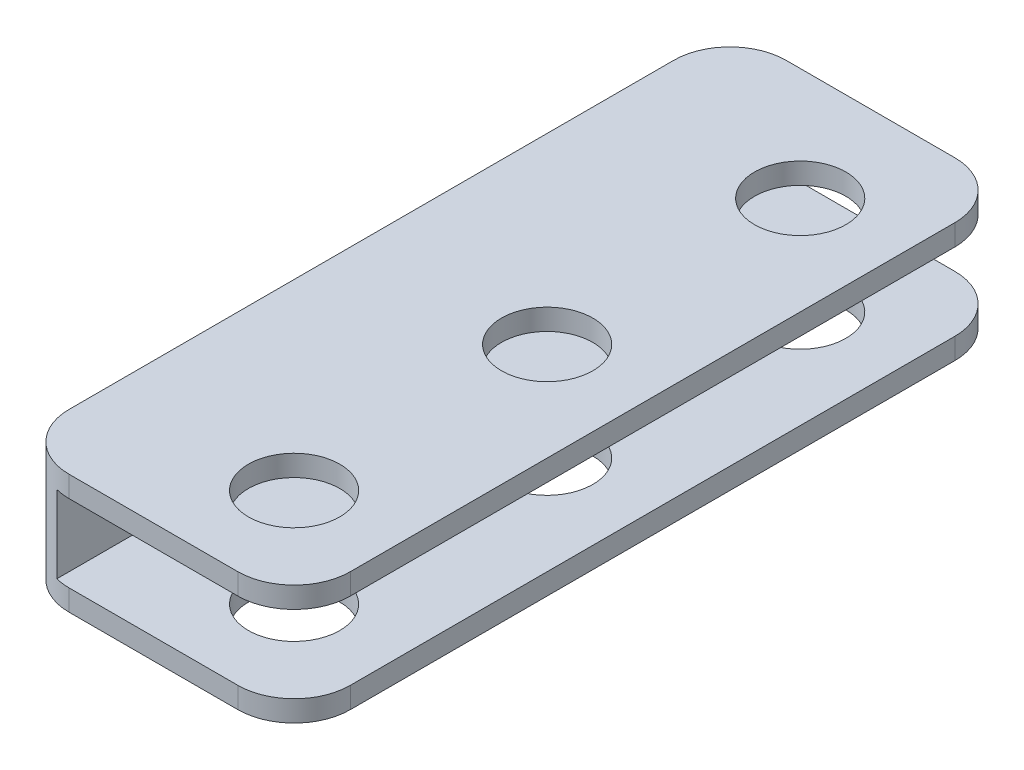
SolidWorks part; units mm, degrees
ref_plane "Płaszczyzna przednia" through (0, 0, 0) normal (0, 0, 1) x (1, 0, 0)
ref_plane "Płaszczyzna górna" through (0, 0, 0) normal (0, 1, 0) x (1, 0, 0)
ref_plane "Płaszczyzna prawa" through (0, 0, 0) normal (1, 0, 0) x (0, 0, -1)
sketch "Sketch1" plane through (0, 0, 0) normal (0, 1, 0) x (1, 0, 0)
  line L1 (-10, -25.5) -> (10, -25.5)
  line L2 (-10, -25.5) -> (-10, 25.5)
  line L3 (-10, 25.5) -> (10, 25.5)
  line L4 (10, -25.5) -> (10, 25.5)
  line L5 (-10, -25.5) -> (10, 25.5) construction
  line L6 (-10, 25.5) -> (10, -25.5) construction
  point P0 (0, 0)
  dimension "D1" = 51
  dimension "D2" = 20
extrude "Boss-Extrude1" add sketch "Sketch1" along normal blind 1.5
sketch "Sketch2" plane through (0, 1.5, 0) normal (0, 1, 0) x (1, 0, 0)
  line L0 (-10, -25.5) -> (10, -25.5) construction
  line L1 (-10, 25.5) -> (-7, 25.5)
  line L2 (-10, 25.5) -> (-10, -25.5)
  line L3 (-10, -25.5) -> (-7, -25.5)
  line L4 (-7, 25.5) -> (-7, -25.5)
  dimension "D1" = 3
extrude "Boss-Extrude2" add sketch "Sketch2" along normal blind 5.5
sketch "Sketch3" plane through (0, 7, 0) normal (0, 1, 0) x (1, 0, 0)
  line L1 (-10, 25.5) -> (10, 25.5)
  line L2 (-10, 25.5) -> (-10, -25.5)
  line L3 (-10, -25.5) -> (10, -25.5)
  line L4 (10, 25.5) -> (10, -25.5)
extrude "Boss-Extrude3" add sketch "Sketch3" along normal blind 1.5
sketch "Sketch4" plane through (0, 8.5, 0) normal (0, 1, 0) x (1, 0, 0)
  line L0 (-7, 25.5) -> (-7, -25.5) construction
  line L1 (-10, -25.5) -> (10, -25.5) construction
  line L2 (3, 25.5) -> (3, -25.5) construction
  line L3 (10, 25.5) -> (-10, 25.5) construction
  line L4 (-10, 25.5) -> (-10, -25.5) construction
  circle A0 centre (3, 17.5) radius 3.25
  circle A1 centre (3, -0.5) radius 3.25
  circle A2 centre (3, -18.5) radius 3.25
  dimension "D3" = 8
  dimension "D1" = 3
  dimension "D2" = 10
  dimension "D4" = 36
  dimension "D5" = 18
extrude "Cut-Extrude1" cut sketch "Sketch4" against normal blind 15
fillet "Fillet1" radius 4 6 edges at (-10, 4.25, 25.5) (-10, 4.25, -25.5) (10, 0.75, 25.5) (10, 7.75, 25.5) (10, 0.75, -25.5) (10, 7.75, -25.5)
